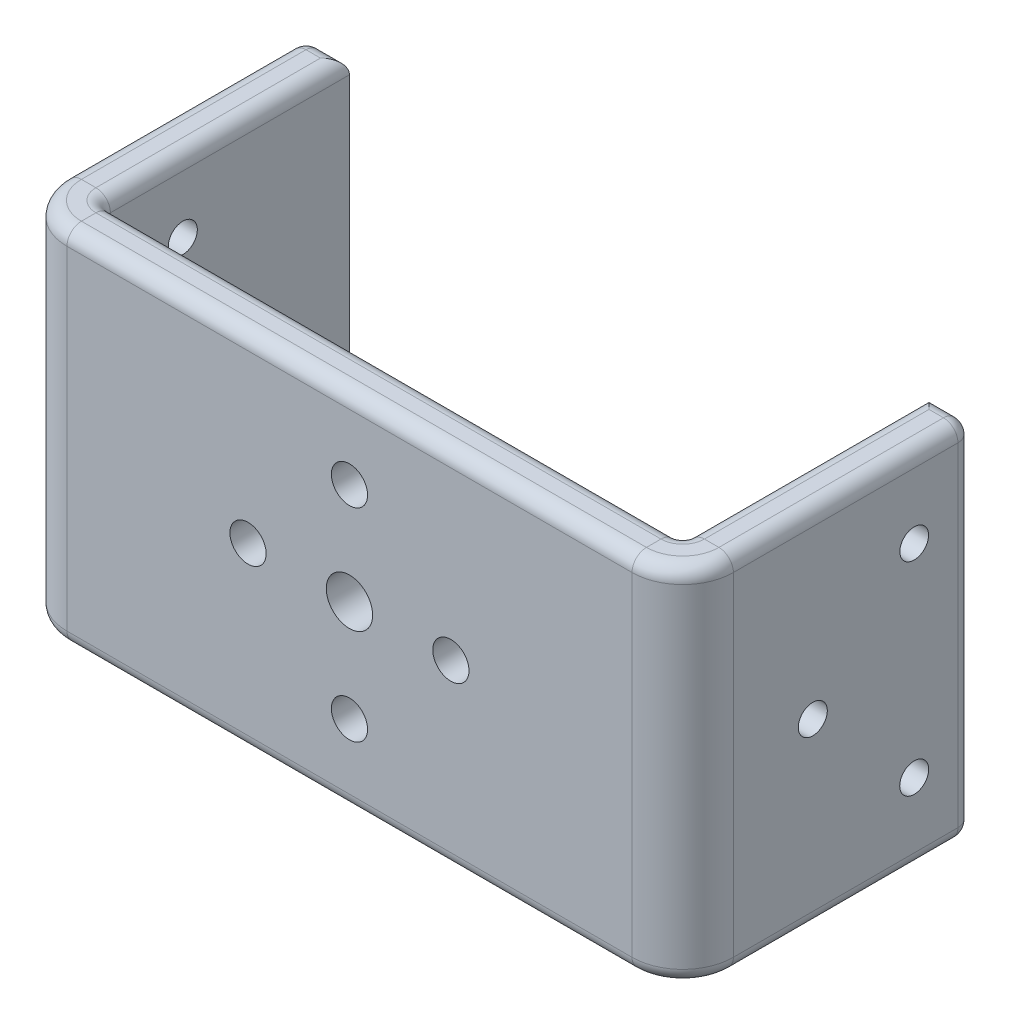
SolidWorks part; units mm, degrees
note: The reader was unsure of these and kept them because the rebuilt part matched: thickness of "Base-Flange1", "Edge-Flange1", "Edge-Flange2", "Sheet-Metal2", "Sheet-Metal3", "Sheet-Metal4", "Sheet-Metal5", "Sheet-Metal6", "Sheet-Metal7"; flange length of "Edge-Flange1", "Edge-Flange2".
ref_plane "Front" through (0, 0, 0) normal (0, 0, 1) x (1, 0, 0)
ref_plane "Top" through (0, 0, 0) normal (0, 1, 0) x (1, 0, 0)
ref_plane "Right" through (0, 0, 0) normal (1, 0, 0) x (0, 0, -1)
sketch "Sketch1" plane through (0, 0, 0) normal (0, 0, 1) x (1, 0, 0)
  line L1 (-20, 12.5) -> (20, 12.5)
  line L2 (-20, 12.5) -> (-20, -12.5)
  line L3 (-20, -12.5) -> (20, -12.5)
  line L4 (20, 12.5) -> (20, -12.5)
  line L5 (-20, 12.5) -> (20, -12.5) construction
  line L6 (-20, -12.5) -> (20, 12.5) construction
  point P0 (0, 0)
  dimension "D1" = 40
  dimension "D2" = 25
base flange "Base-Flange1" sketch "Sketch1" thickness 3 reverse thickness direction no parameters "D1"=0.5
edge flange "Edge-Flange1" sketch "Sketch8" flange angle 90 flange length 20 flange position material outside bend radius 0.5 thickness 3 relief rectangular parameters "D1"=0.7366, "D6"=10
sketch "Sketch8" plane through (20, 0, -3) normal (1, 0, 0) x (0, -1, 0)
  line L0 (12.5, 0) -> (-12.5, 0) construction
  line L1 (12.5, 0) -> (-12.5, 0)
  line L2 (-12.5, 0) -> (-12.5, 17)
  line L3 (-12.5, 17) -> (12.5, 17)
  line L4 (12.5, 17) -> (12.5, 0)
bend "EdgeBend1" bend radius 0.5 bend angle 90 parameters "D5"=1
edge flange "Edge-Flange2" sketch "Sketch11" flange angle 90 flange length 20 flange position material outside bend radius 0.5 thickness 3 relief rectangular parameters "D1"=0.7366, "D6"=10
sketch "Sketch11" plane through (-20, 0, -3) normal (-1, 0, 0) x (0, 1, 0)
  line L0 (12.5, 0) -> (-12.5, 0) construction
  line L1 (12.5, 0) -> (-12.5, 0)
  line L2 (-12.5, 0) -> (-12.5, 17)
  line L3 (-12.5, 17) -> (12.5, 17)
  line L4 (12.5, 17) -> (12.5, 0)
bend "EdgeBend2" bend radius 0.5 bend angle 90 parameters "D5"=2
extrude "Cut-Extrude1" cut sketch "Sketch12" along normal blind 7
sketch "Sketch12" plane through (-20, 10.2122, -95) normal (-1, 0, 0) x (0, -1, 0)
  arc A4 (17.7122, 87.5) -> (17.7122, 85.5) centre (17.7122, 86.5) ccw
  arc A5 (17.7122, 85.5) -> (17.7122, 87.5) centre (17.7122, 86.5) ccw
  arc A6 (2.7122, 87.5) -> (2.7122, 85.5) centre (2.7122, 86.5) ccw
  arc A7 (2.7122, 85.5) -> (2.7122, 87.5) centre (2.7122, 86.5) ccw
extrude "Cut-Extrude2" cut sketch "Sketch13" along normal blind 6
sketch "Sketch13" plane through (20, 10.2122, -95) normal (1, 0, 0) x (0, 1, 0)
  arc A6 (-3.2122, 80.01) -> (-3.2122, 78.03) centre (-3.2122, 79.02) ccw
  arc A7 (-3.2122, 78.03) -> (-3.2122, 80.01) centre (-3.2122, 79.02) ccw
  arc A8 (-17.2122, 80.02) -> (-17.2122, 78.02) centre (-17.2122, 79.02) ccw
  arc A9 (-17.2122, 78.02) -> (-17.2122, 80.02) centre (-17.2122, 79.02) ccw
  arc A10 (-10.2122, 87.02) -> (-10.2122, 85.02) centre (-10.2122, 86.02) ccw
  arc A11 (-10.2122, 85.02) -> (-10.2122, 87.02) centre (-10.2122, 86.02) ccw
fillet "Fillet1" radius 1 12 edges at (0, 12.5, 0) (21.9749, 12.5, -1.0251) (21.9749, -12.5, -1.0251) (23, -12.5, -11.75) (23, 0, -20) (23, 12.5, -11.75) (0, -12.5, 0) (-21.9749, -12.5, -1.0251) (-21.9749, 12.5, -1.0251) (-23, 12.5, -11.75) (-23, 0, -20) (-23, -12.5, -11.75)
fillet "Fillet2" radius 1 18 edges at (21, -12.5, -20) (21, 12.5, -20) (-21, -12.5, -20) (-21, 12.5, -20) (-22.7071, 12.2071, -19.7071) (-22.7071, -12.2071, -19.7071) (22.7071, 12.2071, -19.7071) (22.7071, -12.2071, -19.7071) (0, 12.5, -3) (19.8536, 12.5, -3.1464) (19.8536, -12.5, -3.1464) (20, -12.5, -11.75) (20, 12.5, -11.75) (0, -12.5, -3) (-19.8536, -12.5, -3.1464) (-19.8536, 12.5, -3.1464) (-20, 12.5, -11.75) (-20, -12.5, -11.75)
extrude "Cut-Extrude3" cut sketch "Sketch14" against normal blind 14
sketch "Sketch14" plane through (1.8424, 10.2122, 0) normal (0, 0, 1) x (0, 1, 0)
  arc A8 (-8.9622, 8.8424) -> (-11.4622, 8.8424) centre (-10.2122, 8.8424) ccw
  arc A9 (-11.4622, 8.8424) -> (-8.9622, 8.8424) centre (-10.2122, 8.8424) ccw
  arc A10 (-3.2122, 0.5924) -> (-3.2122, 3.0924) centre (-3.2122, 1.8424) ccw
  arc A11 (-3.2122, 3.0924) -> (-3.2122, 0.5924) centre (-3.2122, 1.8424) ccw
  arc A12 (-17.2122, 0.5924) -> (-17.2122, 3.0924) centre (-17.2122, 1.8424) ccw
  arc A13 (-17.2122, 3.0924) -> (-17.2122, 0.5924) centre (-17.2122, 1.8424) ccw
  arc A14 (-11.4622, -5.1576) -> (-8.9622, -5.1576) centre (-10.2122, -5.1576) ccw
  arc A15 (-8.9622, -5.1576) -> (-11.4622, -5.1576) centre (-10.2122, -5.1576) ccw
  arc A18 (-10.2122, 0.2424) -> (-10.2122, 3.4424) centre (-10.2122, 1.8424) ccw
  arc A19 (-10.2122, 3.4424) -> (-10.2122, 0.2424) centre (-10.2122, 1.8424) ccw
ref_plane "Plane3" through (0, 0, -6) normal (0, 0, -1) x (-1, 0, 0)
sketch "Bend-Lines1" [suppressed] plane through (0, 0, 0) normal (0, 1, 0) x (1, 0, 0)
sketch "Bounding-Box1" [suppressed] plane through (0, 0, 0) normal (0, 1, 0) x (1, 0, 0)
sheet metal parameters "Sheet-Metal2" thickness 3 parameters "D1"=0.7366, "D7"=5
flat pattern "Flat-Pattern2" [suppressed]
sketch "Bend-Lines2" plane through (0, 0, 0) normal (0, 1, 0) x (1, 0, 0)
sketch3d "Bounding-Box2" [suppressed]
  line L0 (25, -15, 0) -> (-25, -15, 0) construction
  line L1 (25, 15, 0) -> (-25, 15, 0) construction
  line L2 (25, -15, 0) -> (25, 15, 0) construction
  line L3 (-25, -15, 0) -> (-25, 15, 0) construction
sheet metal parameters "Sheet-Metal3" thickness 3 parameters "D1"=0.7366, "D7"=5
flat pattern "Flat-Pattern2"
sketch "Bend-Lines2" plane through (0, 0, 0) normal (0, 0, 1) x (1, 0, 0)
  line L0 (26.8054, -15) -> (26.8054, 15) construction
  line L1 (26.8054, -15) -> (26.8054, 15) construction
sketch3d "Bounding-Box2" [suppressed]
  line L0 (-25, -15, 0) -> (45.3474, -15, 0) construction
  line L1 (-25, 15, 0) -> (45.3474, 15, 0) construction
  line L2 (-25, -15, 0) -> (-25, 15, 0) construction
  line L3 (45.3474, -15, 0) -> (45.3474, 15, 0) construction
bend of the flat pattern "Flatten-<EdgeBend1>1"
sheet metal parameters "Sheet-Metal4" thickness 3 parameters "D1"=0.7366, "D7"=5
flat pattern "Flat-Pattern2"
sketch "Bend-Lines2" plane through (0, 0, 0) normal (0, 0, 1) x (1, 0, 0)
  line L0 (21.0708, -12.5) -> (21.0708, 12.5) construction
  line L1 (21.0708, -12.5) -> (21.0708, 12.5) construction
  line L2 (-21.0708, 12.5) -> (-21.0708, -12.5) construction
  line L3 (-21.0708, 12.5) -> (-21.0708, -12.5) construction
sketch3d "Bounding-Box2" [suppressed]
  line L0 (-39.1416, -12.5, 0) -> (39.1416, -12.5, 0) construction
  line L1 (-39.1416, 12.5, 0) -> (39.1416, 12.5, 0) construction
  line L2 (-39.1416, -12.5, 0) -> (-39.1416, 12.5, 0) construction
  line L3 (39.1416, -12.5, 0) -> (39.1416, 12.5, 0) construction
bend of the flat pattern "Flatten-<EdgeBend1>1"
bend of the flat pattern "Flatten-<EdgeBend2>1"
sheet metal parameters "Sheet-Metal5" thickness 3 parameters "D1"=0.7366, "D7"=5
flat pattern "Flat-Pattern2"
sketch "Bend-Lines2" plane through (0, 0, 0) normal (0, 0, 1) x (1, 0, 0)
  line L0 (21.0708, -12.5) -> (21.0708, 12.5) construction
  line L1 (21.0708, -12.5) -> (21.0708, 12.5) construction
  line L2 (-21.0708, 12.5) -> (-21.0708, -12.5) construction
  line L3 (-21.0708, 12.5) -> (-21.0708, -12.5) construction
sketch3d "Bounding-Box2" [suppressed]
  line L0 (-39.1416, -12.5, 0) -> (39.1416, -12.5, 0) construction
  line L1 (-39.1416, 12.5, 0) -> (39.1416, 12.5, 0) construction
  line L2 (-39.1416, -12.5, 0) -> (-39.1416, 12.5, 0) construction
  line L3 (39.1416, -12.5, 0) -> (39.1416, 12.5, 0) construction
bend of the flat pattern "Flatten-<EdgeBend1>1"
bend of the flat pattern "Flatten-<EdgeBend2>1"
sheet metal parameters "Sheet-Metal6" thickness 3 parameters "D1"=0.7366, "D7"=5
flat pattern "Flat-Pattern2"
sketch "Bend-Lines2" plane through (0, 0, 0) normal (0, 0, 1) x (1, 0, 0)
  line L0 (21.0708, -11.5) -> (21.0708, 11.5) construction
  line L1 (21.0708, -11.5) -> (21.0708, 11.5) construction
  line L2 (-21.0708, 11.5) -> (-21.0708, -11.5) construction
  line L3 (-21.0708, 11.5) -> (-21.0708, -11.5) construction
sketch3d "Bounding-Box2" [suppressed]
  line L0 (-39.1416, -12.5, 0) -> (39.1416, -12.5, 0) construction
  line L1 (-39.1416, 12.5, 0) -> (39.1416, 12.5, 0) construction
  line L2 (-39.1416, -12.5, 0) -> (-39.1416, 12.5, 0) construction
  line L3 (39.1416, -12.5, 0) -> (39.1416, 12.5, 0) construction
bend of the flat pattern "Flatten-<EdgeBend1>1"
bend of the flat pattern "Flatten-<EdgeBend2>1"
sheet metal parameters "Sheet-Metal7" thickness 3 parameters "D1"=0.7366, "D7"=5
flat pattern "Flat-Pattern2"
sketch "Bend-Lines2" plane through (0, 0, 0) normal (0, 0, 1) x (1, 0, 0)
  line L0 (21.0708, -11.5) -> (21.0708, 11.5) construction
  line L1 (21.0708, -11.5) -> (21.0708, 11.5) construction
  line L2 (-21.0708, 11.5) -> (-21.0708, -11.5) construction
  line L3 (-21.0708, 11.5) -> (-21.0708, -11.5) construction
sketch3d "Bounding-Box2" [suppressed]
  line L0 (-39.1416, -12.5, 0) -> (39.1416, -12.5, 0) construction
  line L1 (-39.1416, 12.5, 0) -> (39.1416, 12.5, 0) construction
  line L2 (-39.1416, -12.5, 0) -> (-39.1416, 12.5, 0) construction
  line L3 (39.1416, -12.5, 0) -> (39.1416, 12.5, 0) construction
bend of the flat pattern "Flatten-<EdgeBend1>1"
bend of the flat pattern "Flatten-<EdgeBend2>1"
